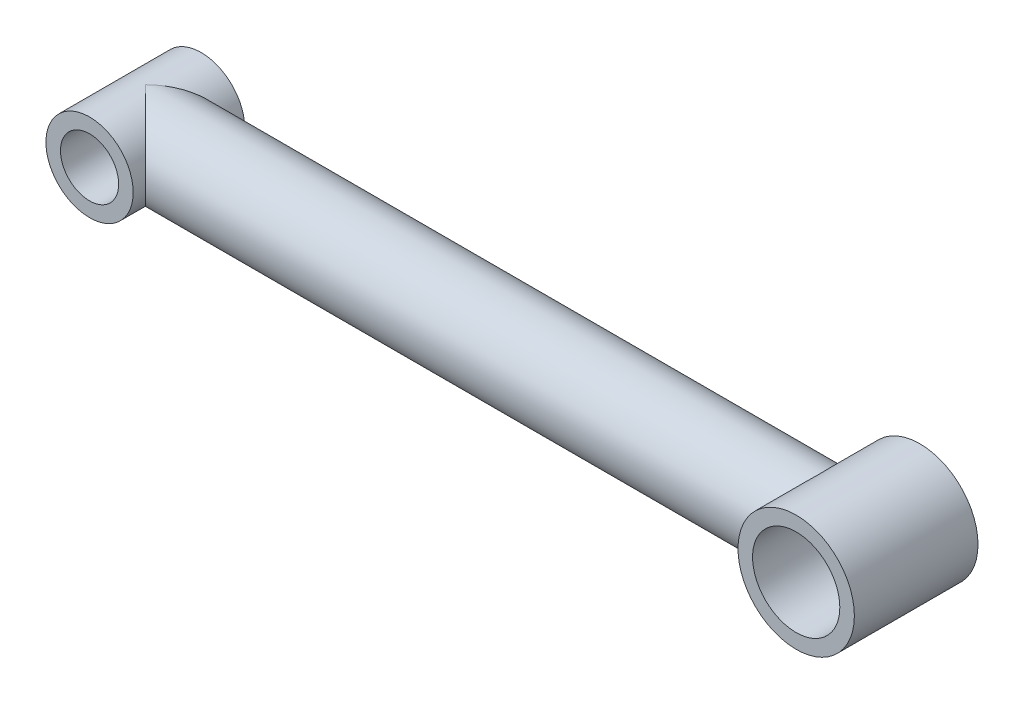
SolidWorks part; units mm, degrees
material "AISI 1035 Steel (SS)"
ref_plane "Front Plane" through (0, 0, 0) normal (0, 0, 1) x (1, 0, 0)
ref_plane "Top Plane" through (0, 0, 0) normal (0, 1, 0) x (1, 0, 0)
ref_plane "Right Plane" through (0, 0, 0) normal (1, 0, 0) x (0, 0, -1)
sketch "Sketch1" plane through (0, 0, 0) normal (1, 0, 0) x (0, 0, -1)
  circle A0 centre (0, 0) radius 4.8387
extrude "Boss-Extrude1" add sketch "Sketch1" along normal blind 39.516 and the other way blind 39.516
sketch "Sketch2" plane through (0, 0, 0) normal (0, 0, 1) x (1, 0, 0)
  line L1 (-39.516, 4.8387) -> (-39.516, -4.8387) construction
  circle A3 centre (-39.516, 0) radius 4.8387
extrude "Boss-Extrude2" add sketch "Sketch2" along normal blind 6.1887 and the other way blind 6.1887
sketch "Sketch3" plane through (0, 0, 6.1887) normal (0, 0, 1) x (1, 0, 0)
  circle A0 centre (-39.516, 0) radius 3.2258
extrude "Cut-Extrude1" cut sketch "Sketch3" against normal through all
sketch "Sketch4" plane through (0, 0, 0) normal (0, 0, 1) x (1, 0, 0)
  line L0 (39.516, -4.8387) -> (39.516, 4.8387) construction
  circle A0 centre (39.516, 0) radius 6.4516
extrude "Boss-Extrude3" add sketch "Sketch4" along normal blind 6.8555 and the other way blind 6.8555
sketch "Sketch5" plane through (0, 0, 6.8555) normal (0, 0, 1) x (1, 0, 0)
  circle A0 centre (39.516, 0) radius 4.8387
extrude "Cut-Extrude2" cut sketch "Sketch5" against normal through all
